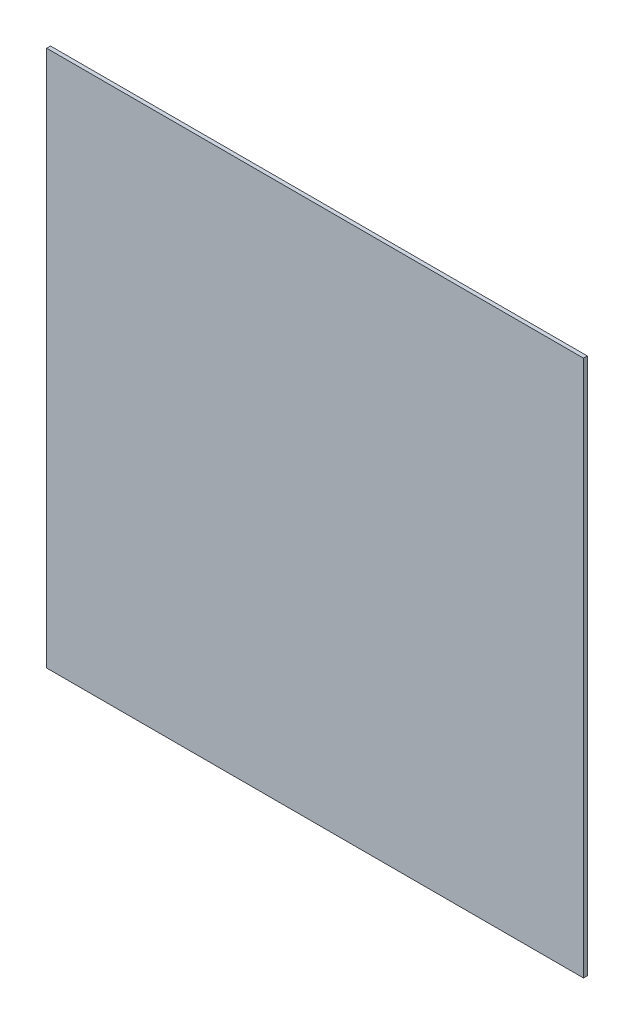
SolidWorks part; units mm, degrees
ref_plane "Front Plane" through (0, 0, 0) normal (0, 0, 1) x (1, 0, 0)
ref_plane "Top Plane" through (0, 0, 0) normal (0, 1, 0) x (1, 0, 0)
ref_plane "Right Plane" through (0, 0, 0) normal (1, 0, 0) x (0, 0, -1)
sketch "Sketch1" plane through (0, 0, 0) normal (0, 0, 1) x (1, 0, 0)
  line L4 (-79.9084, 73.8886) -> (-97.6376, 73.8886)
  line L5 (-97.6376, 73.8886) -> (-97.6376, 56.1594)
  line L6 (-97.6376, 56.1594) -> (-79.9084, 56.1594)
  line L7 (-79.9084, 56.1594) -> (-79.9084, 73.8886)
  line L8 (-79.9084, 73.8886) -> (-97.6376, 73.8886)
  line L9 (-97.6376, 73.8886) -> (-97.6376, 56.1594)
  line L10 (-97.6376, 56.1594) -> (-79.9084, 56.1594)
  line L11 (-79.9084, 56.1594) -> (-79.9084, 73.8886)
  dimension "D1" = 0
extrude "Boss-Extrude1" add sketch "Sketch1" along normal blind 0.127
sketch "Sketch2" plane through (0, 0, 0) normal (0, 0, -1) x (-1, 0, 0)
  line L0 (97.6376, 65.024) -> (79.9084, 65.024) construction
  line L1 (97.6376, 73.8886) -> (97.6376, 56.1594) construction
  line L2 (79.9084, 56.1594) -> (79.9084, 73.8886) construction
  line L3 (79.9084, 57.1754) -> (97.6376, 57.1754) construction
  line L4 (97.6376, 62.1919) -> (79.9084, 62.1919) construction
  line L5 (79.9084, 56.1594) -> (79.9084, 73.8886) construction
  line L6 (97.6376, 73.8886) -> (97.6376, 56.1594) construction
  line L7 (86.233, 57.1754) -> (89.1133, 57.1754)
  line L8 (89.1133, 57.1754) -> (91.313, 60.9854)
  line L9 (91.313, 60.9854) -> (88.4327, 60.9854)
  line L10 (88.4327, 60.9854) -> (86.233, 57.1754)
  line L11 (88.773, 73.8886) -> (88.773, 56.1594) construction
  line L12 (79.9084, 73.8886) -> (97.6376, 73.8886) construction
  line L13 (97.6376, 56.1594) -> (79.9084, 56.1594) construction
  line L14 (81.4477, 57.1754) -> (84.328, 57.1754)
  line L15 (84.328, 57.1754) -> (86.5277, 60.9854)
  line L16 (86.5277, 60.9854) -> (83.6474, 60.9854)
  line L17 (83.6474, 60.9854) -> (81.4477, 57.1754)
  line L18 (91.0183, 57.1754) -> (93.218, 60.9854)
  line L19 (93.218, 60.9854) -> (96.0983, 60.9854)
  line L20 (96.0983, 60.9854) -> (93.8986, 57.1754)
  line L21 (93.8986, 57.1754) -> (91.0183, 57.1754)
  line L22 (79.9084, 72.8726) -> (97.6376, 72.8726) construction
  line L23 (86.233, 69.0626) -> (89.1133, 69.0626)
  line L24 (89.1133, 69.0626) -> (91.313, 72.8726)
  line L25 (91.313, 72.8726) -> (88.4327, 72.8726)
  line L26 (88.4327, 72.8726) -> (86.233, 69.0626)
  line L27 (81.4477, 69.0626) -> (84.328, 69.0626)
  line L28 (84.328, 69.0626) -> (86.5277, 72.8726)
  line L29 (86.5277, 72.8726) -> (83.6474, 72.8726)
  line L30 (83.6474, 72.8726) -> (81.4477, 69.0626)
  line L31 (91.0183, 69.0626) -> (93.218, 72.8726)
  line L32 (93.218, 72.8726) -> (96.0983, 72.8726)
  line L33 (96.0983, 72.8726) -> (93.8986, 69.0626)
  line L34 (93.8986, 69.0626) -> (91.0183, 69.0626)
  line L35 (87.6731, 57.1754) -> (89.8729, 60.9854) construction
  text T0 "<b>FIRE</b>" font "GordonURWMed" height in points 24
  point P18 (87.6731, 57.1754)
  point P26 (89.8729, 60.9854)
  point P40 (87.6731, 69.0626)
  point P43 (89.8729, 72.8726)
  point P53 (88.773, 59.0804)
  dimension "D1" = 2.8321
  dimension "D2" = 60
  dimension "D3" = 3.81
  dimension "D4" = 5.08
  dimension "D5" = 1.905
  dimension "D6" = 1.905
  dimension "D7" = 1.016
  dimension "D8" = 1.016
  dimension "D9" = 2
wrap "FIRE" sketch "Sketch2" wrap type scribe source sketch "Sketch2" face at (-88.773, 65.024, 0)
sketch "Sketch3" [suppressed] plane through (0, 0, 0) normal (0, 0, -1) x (-1, 0, 0)
  line L0 (79.9084, 65.3056) -> (97.6376, 65.3056) construction
  line L1 (79.9084, 56.1594) -> (79.9084, 73.8886) construction
  line L2 (97.6376, 73.8886) -> (97.6376, 56.1594) construction
  line L3 (79.9084, 65.024) -> (97.6376, 65.024) construction
  line L4 (79.9084, 60.5059) -> (97.6376, 60.5059) construction
  line L5 (79.9084, 69.5421) -> (97.6376, 69.5421) construction
  line L6 (95.8049, 69.5421) -> (95.8049, 60.5059) construction
  text T0 "APU" font "GordonURWMed" height in points 18
  text T1 "FIRE" font "GordonURWMed" height in points 18
  point P15 (95.8049, 65.024)
wrap "APU FIRE" [suppressed] sketch "Sketch3" source sketch "Sketch3"
sketch "Sketch4" [suppressed] plane through (0, 0, 0) normal (0, 0, -1) x (-1, 0, 0)
  line L0 (79.9084, 65.4564) -> (97.6376, 65.4564) construction
  line L1 (79.9084, 56.1594) -> (79.9084, 73.8886) construction
  line L2 (97.6376, 73.8886) -> (97.6376, 56.1594) construction
  line L4 (79.9084, 65.024) -> (97.6376, 65.024) construction
  line L6 (79.9084, 61.4926) -> (97.6376, 61.4926) construction
  text T0 "MASTER" font "GordonURWCon" height in points 14
  text T1 "CAUTION" font "GordonURWCon" height in points 14
wrap "MC" [suppressed] sketch "Sketch4" source sketch "Sketch4"
